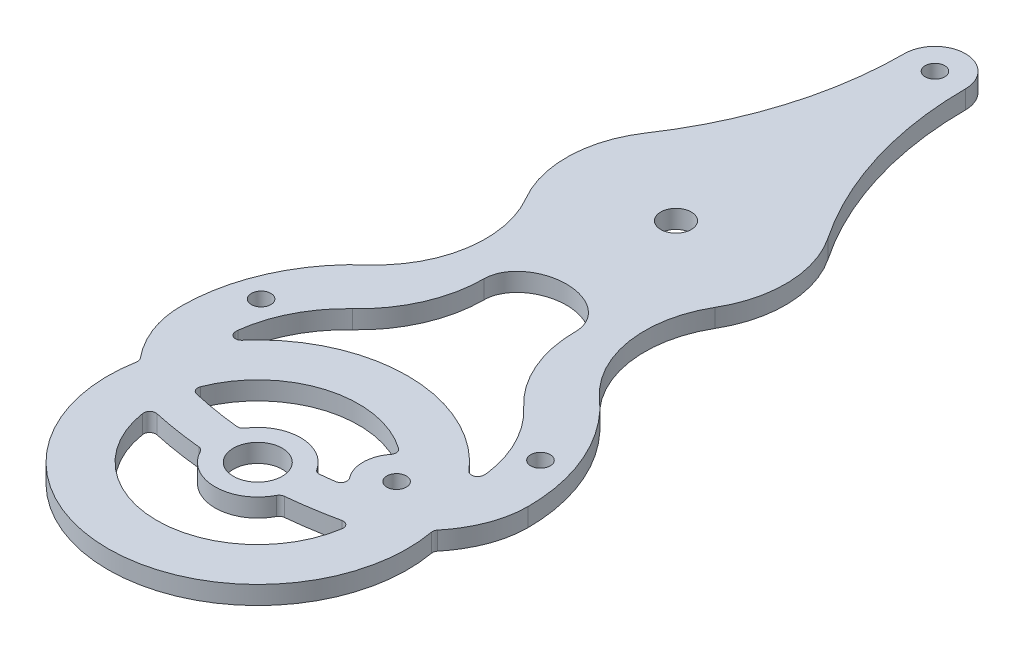
SolidWorks part; units mm, degrees
ref_plane "Front Plane" through (0, 0, 0) normal (0, 0, 1) x (1, 0, 0)
ref_plane "Top Plane" through (0, 0, 0) normal (0, 1, 0) x (1, 0, 0)
ref_plane "Right Plane" through (0, 0, 0) normal (1, 0, 0) x (0, 0, -1)
sketch "Sketch1" plane through (0, 0, 0) normal (0, 1, 0) x (1, 0, 0)
  line L1 (0, -52.0078) -> (0, -64.2302) construction
  circle A8 centre (0, -68.5564) radius 24.5485
  circle A9 centre (0, -68.5564) radius 8.2743 construction
  circle A10 centre (0, -68.5564) radius 16.5485
  ellipse E0 centre (0, -51.4173) end of major axis (20.3628, -51.4173) minor radius 12.813 construction
  point P0 (0, -52.0078)
  point P1 (0, -44.0078)
  dimension "D2" = 49.0971
  dimension "D3" = 33.0971
  dimension "D1" = 8
extrude "Boss-Extrude1" add sketch "Sketch1" along normal blind 3
sketch "Sketch2" plane through (0, 0, 0) normal (0, -1, 0) x (1, 0, 0)
  line L0 (0, 71.5564) -> (0, 65.5564) construction
  line L5 (-24.5125, 67.2269) -> (-23.4288, 61.2269)
  line L6 (24.5125, 67.2269) -> (23.4288, 61.2269)
  circle A1 centre (0, 0) radius 68.5564 construction
  arc A2 (-24.5125, 67.2269) -> (24.5125, 67.2269) centre (0, 0) cw
  arc A3 (-23.4288, 61.2269) -> (23.4288, 61.2269) centre (0, 0) cw
  circle A4 centre (0, 68.5564) radius 24.5485 construction
  point P10 (0, 68.5564)
  dimension "D1" = 6
extrude "Boss-Extrude2" add sketch "Sketch2" against normal up to surface (3 mm away) up to face at (0, 3, 93.1049)
sketch "Sketch4" plane through (0, 0, 0) normal (0, -1, 0) x (1, 0, 0)
  arc A1 (11.2067, 64.5914) -> (10.512, 55.7754) centre (14.1202, 59.9265) ccw
  arc A2 (10.512, 55.7754) -> (15.7966, 63.6247) centre (0, 68.5564) ccw
  circle A3 centre (14.1202, 59.9265) radius 5.5 construction
  circle A4 centre (0, 68.5564) radius 16.5485 construction
  circle A6 centre (0, 68.5564) radius 7
  arc A7 (23.4288, 61.2269) -> (-23.4288, 61.2269) centre (0, 0) ccw construction
  arc A8 (11.2067, 64.5914) -> (15.7966, 63.6247) centre (0, 0) cw
  dimension "D2" = 14
extrude "Boss-Extrude3" add sketch "Sketch4" against normal up to surface (3 mm away) up to face at (0, 3, 93.1049)
fillet "Fillet1" radius 1 9 edges at (10.512, 1.5, 55.7754) (16.514, 1.5, 69.6247) (6.4549, 1.5, 71.2647) (-6.4549, 1.5, 71.2647) (-16.514, 1.5, 69.6247) (-15.7966, 1.5, 63.6247) (-6.1777, 1.5, 65.2647) (6.1777, 1.5, 65.2647) (11.2067, 1.5, 64.5914)
sketch "Sketch5" plane through (0, 3, 0) normal (0, 1, 0) x (1, 0, 0)
  circle A0 centre (0, -68.5564) radius 4
  circle A1 centre (14.1202, -59.9265) radius 1.6
  circle A2 centre (0, -68.5564) radius 7 construction
  arc A3 (10.512, -55.7754) -> (11.2067, -64.5914) centre (14.1202, -59.9265) ccw construction
  dimension "D1" = 3.2
  dimension "D2" = 8
extrude "Cut-Extrude1" cut sketch "Sketch5" against normal through all
sketch "Sketch6" plane through (0, 0, 0) normal (0, -1, 0) x (1, 0, 0)
  line L0 (0, -1000) -> (0, 49000) construction
  circle A0 centre (0, 68.5564) radius 24.5485 construction
  arc A1 (-28.4436, 52.6898) -> (-19.0005, 31.5234) centre (0, 52.6898) ccw construction
  arc A2 (-28.4436, 52.6898) -> (-19.0005, 31.5234) centre (0, 52.6898) ccw
  arc A3 (-15.4999, 9.0782) -> (-19.0005, 31.5234) centre (-30.9998, 18.1563) ccw construction
  arc A4 (-15.4999, 9.0782) -> (-19.0005, 31.5234) centre (-30.9998, 18.1563) ccw
  arc A5 (-24.0821, 63.7936) -> (-19.8886, 54.1663) centre (0, 68.5564) ccw
  arc A6 (-20.3628, 51.4173) -> (-14.0127, 38.9787) centre (0.0539, 54.0001) ccw
  arc A7 (-14.0127, 38.9787) -> (-7.5, 23.9574) centre (-28.0794, 23.9574) cw
  circle A8 centre (-22.8961, 45.1123) radius 1.6
  circle A9 centre (-22.8961, 45.1123) radius 1.6 construction
  arc A10 (-5, -42.4463) -> (5, -42.4463) centre (0, -42.4463) ccw construction
  arc A11 (-5, -42.4463) -> (-14.898, -10.0354) centre (-63.0135, -42.4463) ccw construction
  arc A12 (-15.4999, 9.0782) -> (-14.898, -10.0354) centre (0, 0) ccw construction
  arc A13 (-5, -42.4463) -> (5, -42.4463) centre (0, -42.4463) ccw
  arc A14 (-5, -42.4463) -> (-14.898, -10.0354) centre (-63.0135, -42.4463) ccw
  arc A15 (-15.4999, 9.0782) -> (-14.898, -10.0354) centre (0, 0) ccw
  circle A16 centre (0, -42.4463) radius 1.6 construction
  circle A17 centre (0, -42.4463) radius 1.6
  circle A18 centre (0, 0) radius 2.5 construction
  circle A19 centre (0, 0) radius 2.5
  circle A20 centre (22.8961, 45.1123) radius 1.6
  arc A21 (20.3628, 51.4173) -> (14.0127, 38.9787) centre (-0.0539, 54.0001) cw
  arc A22 (14.0127, 38.9787) -> (7.5, 23.9574) centre (28.0794, 23.9574) ccw
  arc A23 (5, -42.4463) -> (14.898, -10.0354) centre (63.0135, -42.4463) cw
  arc A24 (15.4999, 9.0782) -> (14.898, -10.0354) centre (0, 0) cw
  arc A25 (15.4999, 9.0782) -> (19.0005, 31.5234) centre (30.9998, 18.1563) cw
  arc A26 (28.4436, 52.6898) -> (19.0005, 31.5234) centre (0, 52.6898) cw
  arc A27 (24.0821, 63.7936) -> (19.8886, 54.1663) centre (0, 68.5564) cw
  ellipse E0 centre (0, 52.6898) end of major axis (28.4436, 52.6898) minor radius 20.8666 (-24.0821, 63.7936) -> (-28.4436, 52.6898) ccw
  ellipse E1 centre (0, 51.4173) end of major axis (-20.3628, 51.4173) minor radius 12.813 (19.8886, 54.1663) -> (20.3628, 51.4173) cw
  ellipse E2 centre (0, 52.6898) end of major axis (-28.4436, 52.6898) minor radius 20.8666 (28.4436, 52.6898) -> (-28.4436, 52.6898) ccw construction
  ellipse E3 centre (0, 51.4173) end of major axis (20.3628, 51.4173) minor radius 12.813 (-19.8886, 54.1663) -> (-20.3628, 51.4173) ccw
  ellipse E4 centre (0, 52.6898) end of major axis (-28.4436, 52.6898) minor radius 20.8666 (24.0821, 63.7936) -> (28.4436, 52.6898) cw
  ellipse E5 centre (0, 23.9574) end of major axis (-7.5, 23.9574) minor radius 5.9947 (7.5, 23.9574) -> (-7.5, 23.9574) cw
  point P31 (0, 17.9627)
extrude "Boss-Extrude4" add sketch "Sketch6" against normal up to surface (3 mm away) up to face at (0, 3, 72.5564)
fillet "Fillet2" radius 1 4 edges at (19.8886, 1.5, 54.1663) (-19.8886, 1.5, 54.1663) (24.0821, 1.5, 63.7936) (-24.0821, 1.5, 63.7936)
sketch "Sketch7" plane through (0, 3, 0) normal (0, 1, 0) x (1, 0, 0)
  line L0 (-1.5, -11.0841) -> (-1.5, -6) construction
  line L2 (-4.4462, -4.299) -> (-8.8491, -6.8411) construction
  line L4 (-4.4462, -4.299) -> (-8.8491, -6.8411)
  line L5 (-1.5, -11.0841) -> (-1.5, -6)
  arc A2 (-5.6285, -13.8637) -> (-1.5, -11.0841) centre (-4.5, -11.0841) ccw construction
  arc A5 (-8.8491, -6.8411) -> (-9.1921, -11.8063) centre (-7.3491, -9.4392) ccw construction
  arc A6 (-9.1921, -11.8063) -> (-5.6285, -13.8637) centre (0, 0) ccw construction
  arc A7 (-8.8491, -6.8411) -> (-9.1921, -11.8063) centre (-7.3491, -9.4392) ccw
  arc A8 (-9.1921, -11.8063) -> (-5.6285, -13.8637) centre (0, 0) ccw
  arc A9 (-5.6285, -13.8637) -> (-1.5, -11.0841) centre (-4.5, -11.0841) ccw
  arc A10 (-3.3391, -4.3704) -> (-4.4462, -4.299) centre (-3.9462, -5.1651) ccw construction
  arc A11 (-3.3391, -4.3704) -> (-2.1154, -5.0769) centre (0, 0) ccw construction
  arc A12 (-1.5, -6) -> (-2.1154, -5.0769) centre (-2.5, -6) ccw construction
  arc A13 (-3.3391, -4.3704) -> (-4.4462, -4.299) centre (-3.9462, -5.1651) ccw
  arc A14 (-3.3391, -4.3704) -> (-2.1154, -5.0769) centre (0, 0) ccw
  arc A15 (-1.5, -6) -> (-2.1154, -5.0769) centre (-2.5, -6) ccw
extrude "Cut-Extrude2" [suppressed] cut sketch "Sketch7" against normal through all
pattern_circular "CirPattern1" [suppressed] count 6 over 360 of bodies 106
